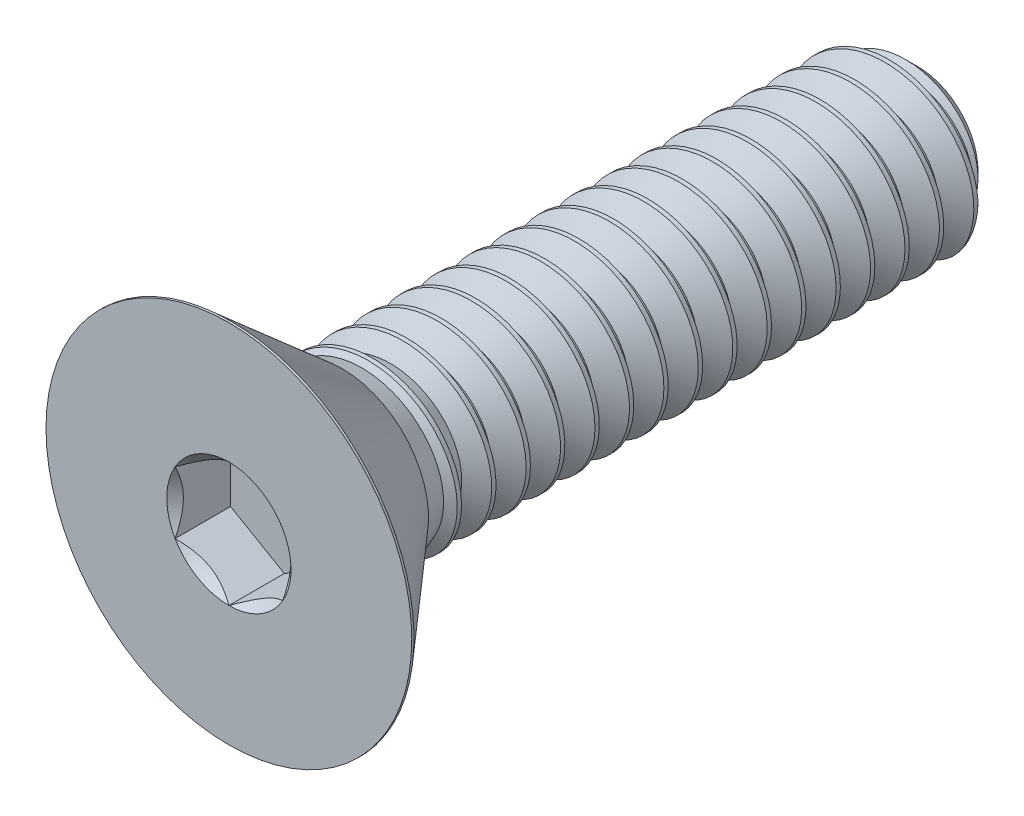
SolidWorks part; units mm, degrees
material "AISI 1020 Steel, Cold Rolled"
ref_plane "Front Plane" through (0, 0, 0) normal (0, 0, 1) x (1, 0, 0)
ref_plane "Top Plane" through (0, 0, 0) normal (0, 1, 0) x (1, 0, 0)
ref_plane "Right Plane" through (0, 0, 0) normal (1, 0, 0) x (0, 0, -1)
sketch "Sketch1" plane through (0, 0, 0) normal (1, 0, 0) x (0, 0, -1)
  line L0 (-12.7, 0) -> (12.7, 0) construction
  line L1 (-12.7, 0) -> (-12.7, 6.7437)
  line L2 (-12.7, 6.7437) -> (-12.6182, 6.7437)
  line L3 (-12.6182, 6.7437) -> (-8.6106, 3.2599)
  line L4 (-12.6182, -6.7437) -> (-8.6106, -3.2599)
  line L5 (12.7, 0) -> (12.7, 3.175)
  line L6 (12.7, 3.175) -> (-8.6106, 3.175)
  line L7 (11.7475, 3.175) -> (12.7, 2.2225)
  line L8 (12.6206, 3.3125) -> (13.2556, 2.2126) construction
  line L9 (13.2556, 2.2126) -> (13.8906, 3.3125) construction
  line L10 (13.8906, 3.3125) -> (12.6206, 3.3125) construction
  line L11 (12.6603, 3.2437) -> (13.8509, 3.2437)
  line L12 (13.8509, 3.2437) -> (13.335, 2.3501)
  line L13 (13.335, 2.3501) -> (13.1762, 2.3501)
  line L14 (13.1762, 2.3501) -> (12.6603, 3.2437)
  line L15 (13.2556, 2.3501) -> (13.2556, 2.2126) construction
  line L16 (12.7, 3.175) -> (13.8112, 3.175) construction
  line L17 (13.2556, 3.3125) -> (13.2556, 3.175) construction
  line L18 (12.7, -3.175) -> (-8.6106, -3.175)
  arc A0 (-8.6106, 3.2599) -> (-8.3834, 3.175) centre (-8.3834, 3.5213) ccw
  point P2 (0, 0)
  point P23 (-10.6553, 0)
  point P27 (13.2556, 3.2437)
  point P30 (10.795, -3.175)
  point P31 (-8.6106, 6.7437)
  point P34 (-12.6182, -6.7437)
  dimension "Length" = 25.4
  dimension "Head Height" = 4.0894
  dimension "Head Diameter" = 13.4874
  dimension "Countersink Angle" = 82
  dimension "Screw Size Decimal Equivalent" = 6.35
  dimension "Pitch" = 1.27
  dimension "D4" = 0.1588
  dimension "D3" = 45
  dimension "D5" = 0.9525
  dimension "D6" = 2.0447
  dimension "D1" = 1.905
  dimension "D7" = 0.0818
sketch "Sketch8" plane through (0, 0, 0) normal (0, 0, 1) x (1, 0, 0)
  line L1 (0, 2.2914) -> (-1.9844, 1.1457)
  line L2 (-1.9844, 1.1457) -> (-1.9844, -1.1457)
  line L3 (-1.9844, -1.1457) -> (0, -2.2914)
  line L4 (0, -2.2914) -> (1.9844, -1.1457)
  line L5 (1.9844, -1.1457) -> (1.9844, 1.1457)
  line L6 (1.9844, 1.1457) -> (0, 2.2914)
  circle A0 centre (0, 0) radius 1.9844 construction
  dimension "Drive Size" = 3.9688
sketch "Sketch2" plane through (0, 0, 0) normal (1, 0, 0) x (0, 0, -1)
  line L0 (-12.6182, 6.7437) -> (-8.6106, 3.2599) construction
  line L1 (-12.7, 0) -> (-12.7, 6.7437) construction
  line L2 (-12.6182, 6.7437) -> (-8.5129, 3.175)
  line L3 (-12.7, 0) -> (-12.7, 6.7437)
  line L4 (-12.7, 6.7437) -> (-12.6182, 6.7437) construction
  line L5 (-12.7, 6.7437) -> (-12.6182, 6.7437)
  line L6 (-8.5129, 3.175) -> (11.7475, 3.175)
  line L7 (11.7475, 3.175) -> (12.7, 2.2225)
  line L8 (12.7, 2.2225) -> (12.7, 0)
  line L9 (12.7, 0) -> (-12.7, 0)
revolve "Revolve1" add sketch "Sketch2" angle 360 about L9
sketch "Sketch9" plane through (0, 0, 12.7) normal (0, 0, 1) x (1, 0, 0)
  line L0 (1.9844, -1.1457) -> (1.9844, 1.1457) construction
  line L1 (0, -2.2914) -> (1.9844, -1.1457) construction
  line L2 (-1.9844, -1.1457) -> (0, -2.2914) construction
  line L3 (-1.9844, 1.1457) -> (-1.9844, -1.1457) construction
  line L4 (0, 2.2914) -> (-1.9844, 1.1457) construction
  line L5 (1.9844, 1.1457) -> (0, 2.2914) construction
  line L6 (1.9844, -1.1457) -> (1.9844, 1.1457)
  line L7 (0, -2.2914) -> (1.9844, -1.1457)
  line L8 (-1.9844, -1.1457) -> (0, -2.2914)
  line L9 (-1.9844, 1.1457) -> (-1.9844, -1.1457)
  line L10 (0, 2.2914) -> (-1.9844, 1.1457)
  line L11 (1.9844, 1.1457) -> (0, 2.2914)
sketch "Sketch10" plane through (0, 0, 12.7) normal (0, 0, 1) x (1, 0, 0)
  circle A0 centre (0, 0) radius 2.2914
extrude "Cut-Extrude2" cut sketch "Sketch10" against normal up to vertex (2.0447 mm away) draft 45 up to point (0, 0, 10.6553)
extrude "Cut-Extrude1" cut sketch "Sketch9" against normal up to vertex (2.0447 mm away) up to point (0, 0, 10.6553)
ref_plane "Plane1" through (0, 0, 8.5129) normal (0, 0, 1) x (1, 0, 0)
split "Split1" trim tools "Plane1" bodies to split 111 resulting bodies 105 106
sketch "Sketch3" plane through (0, 0, -12.7) normal (0, 0, -1) x (-1, 0, 0)
  circle A0 centre (0, 0) radius 3.175 construction
  circle A1 centre (0, 0) radius 3.175
curve "Helix/Spiral1" pitch 1.27 height 25.4 radius 3.175 centre (0, 0, -12.7) axis (0, 0, 1) start towards (0, 1, 0)
sketch "Sketch4" plane through (0, 0, 0) normal (1, 0, 0) x (0, 0, -1)
  line L0 (12.6603, 3.2437) -> (13.8509, 3.2437) construction
  line L1 (13.1762, 2.3501) -> (12.6603, 3.2437) construction
  line L2 (13.335, 2.3501) -> (13.1762, 2.3501) construction
  line L3 (13.8509, 3.2437) -> (13.335, 2.3501) construction
  line L4 (12.6603, 3.2437) -> (13.8509, 3.2437)
  line L5 (13.1762, 2.3501) -> (12.6603, 3.2437)
  line L6 (13.335, 2.3501) -> (13.1762, 2.3501)
  line L7 (13.8509, 3.2437) -> (13.335, 2.3501)
sweep "Cut-Sweep1" cut profiles "Sketch4" path "Helix/Spiral1" align with end faces yes
sketch "Sketch7" plane through (0, 0, 8.5129) normal (0, 0, 1) x (1, 0, 0)
  circle A0 centre (0, 0) radius 3.175
extrude "Boss-Extrude2" add sketch "Sketch7" against normal up to next (21.2129 mm away) draft 20
equation "\"D4@Sketch1\" = \"Pitch@Sketch1\" / 8"
equation "\"D5@Sketch1\"=\"Pitch@Sketch1\"*0.75"
equation "\"D4@Helix/Spiral1\"=\"Pitch@Sketch1\""
equation "\"D3@Helix/Spiral1\"=\"Length@Sketch1\""
equation "\"D6@Sketch1\"=\"Head Height@Sketch1\"/2"
equation "\"D1@Sketch1\"=\"Pitch@Sketch1\"*1.5"
equation "\"D7@Sketch1\"=\"Head Height@Sketch1\"*0.02"
